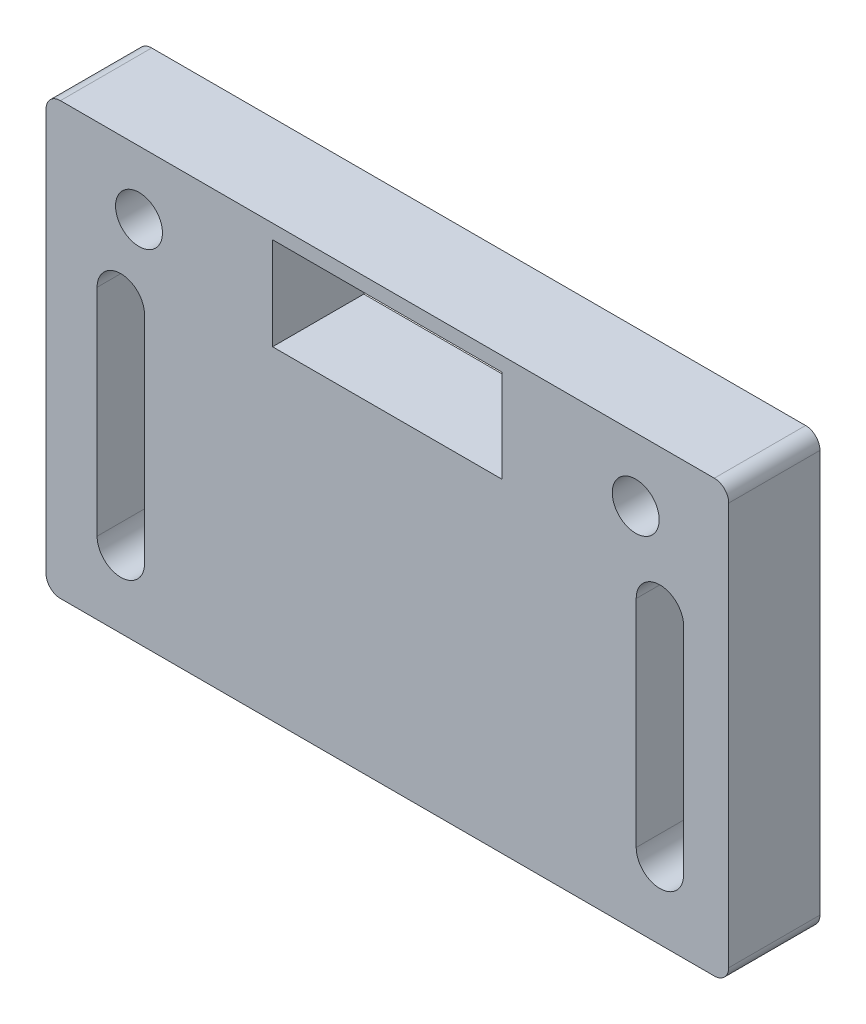
SolidWorks part; units mm, degrees
ref_plane "Front Plane" through (0, 0, 0) normal (0, 0, 1) x (1, 0, 0)
ref_plane "Top Plane" through (0, 0, 0) normal (0, 1, 0) x (1, 0, 0)
ref_plane "Right Plane" through (0, 0, 0) normal (1, 0, 0) x (0, 0, -1)
sketch "Sketch1" plane through (0, 0, 0) normal (0, 0, 1) x (1, 0, 0)
  line L0 (0, -2) -> (15.975, -2)
  line L1 (-47.5, 0) -> (47.5, 0)
  line L2 (-47.5, 0) -> (-47.5, -60)
  line L3 (-47.5, -60) -> (47.5, -60)
  line L4 (47.5, 0) -> (47.5, -60)
  line L5 (15.975, -2) -> (15.975, -14.9)
  line L6 (15.975, -14.9) -> (-15.975, -14.9)
  line L7 (-15.975, -14.9) -> (-15.975, -2)
  line L8 (-15.975, -2) -> (0, -2)
  line L9 (0, 0) -> (0, -2) construction
  dimension "D1" = 95
  dimension "D2" = 60
  dimension "D3" = 12.9
  dimension "D4" = 2
  dimension "D5" = 31.95
extrude "Boss-Extrude1" add sketch "Sketch1" along normal blind 12.7
sketch "Sketch2" plane through (0, 0, 0) normal (0, 0, -1) x (-1, 0, 0)
  line L0 (-47.5, -8.8451) -> (-34.56, -8.8451) construction
  line L1 (-47.5, -60) -> (-47.5, 0) construction
  line L2 (47.5, -8.8451) -> (34.56, -8.8451) construction
  line L3 (47.5, 0) -> (47.5, -60) construction
  line L4 (-34.56, -8.8451) -> (34.56, -8.8451) construction
  dimension "D1" = 69.12
hole_wizard "CSK for 1/4 Flat Head Machine Screw2" positions "Sketch5" profile "Sketch6" countersink size "1/4" standard "ANSI Inch" end condition through all
sketch "Sketch5" plane through (0, 0, 0) normal (0, 0, -1) x (-1, 0, 0)
  point P0 (-34.56, -8.8451)
  point P3 (34.56, -8.8451)
sketch "Sketch6" plane through (34.56, -8.8451, 0) normal (1, 0, 0) x (0, 1, 0)
  line L0 (0, 0) -> (0, 12.7)
  line L1 (0, 12.7) -> (3.2639, 12.7)
  line L2 (3.2639, 12.7) -> (3.2639, 3.6524)
  line L3 (3.2639, 3.6524) -> (6.4389, 0)
  line L5 (6.4389, 0) -> (0, 0)
  line L6 (-3.2639, 3.6524) -> (-6.4389, 0) construction
  line L11 (0, -6.35) -> (0, 107.95) construction
  dimension "Thru Hole Dia." = 6.5278
  dimension "Thru Hole Depth" = 12.7
  dimension "Near C'Sink Dia." = 12.8778
  dimension "Near C'Sink Angle" = 82
fillet "Fillet1" radius 2 2 edges at (-47.5, 0, 6.35) (-47.5, -60, 6.35)
fillet "Fillet2" radius 2 2 edges at (47.5, -60, 6.35) (47.5, 0, 6.35)
sketch "Sketch9" plane through (0, 0, 0) normal (0, 0, -1) x (-1, 0, 0)
  line L0 (-41.2257, -19.9409) -> (-41.2257, -49.9409)
  line L1 (-34.6257, -49.9409) -> (-34.6257, -19.9409)
  line L2 (-47.5, -58) -> (-47.5, -2) construction
  line L3 (-34.6257, -40.8453) -> (33.7943, -40.8453)
  line L4 (33.7943, -49.9409) -> (33.7943, -19.9409)
  line L5 (40.3943, -49.9409) -> (40.3943, -19.9409)
  line L6 (45.5, -60) -> (-45.5, -60) construction
  arc A0 (-34.6257, -49.9409) -> (-41.2257, -49.9409) centre (-37.9257, -49.9409) cw
  arc A1 (-34.6257, -19.9409) -> (-41.2257, -19.9409) centre (-37.9257, -19.9409) ccw
  arc A2 (33.7943, -49.9409) -> (40.3943, -49.9409) centre (37.0943, -49.9409) ccw
  arc A3 (40.3943, -19.9409) -> (33.7943, -19.9409) centre (37.0943, -19.9409) ccw
  dimension "D1" = 3.3
  dimension "D5" = 3.3
  dimension "D8" = 30
  dimension "D2" = 30
  dimension "D3" = 6.2743
  dimension "D4" = 68.42
  dimension "D6" = 10.0591
  dimension "D7" = 10.0591
extrude "Cut-Extrude1" cut sketch "Sketch9" against normal through all contours L1 A1 L0 A0 | L5 A3 L4 A2 region at (37.9257, -34.9409, 0) region at (-37.0943, -34.9409, 0)
